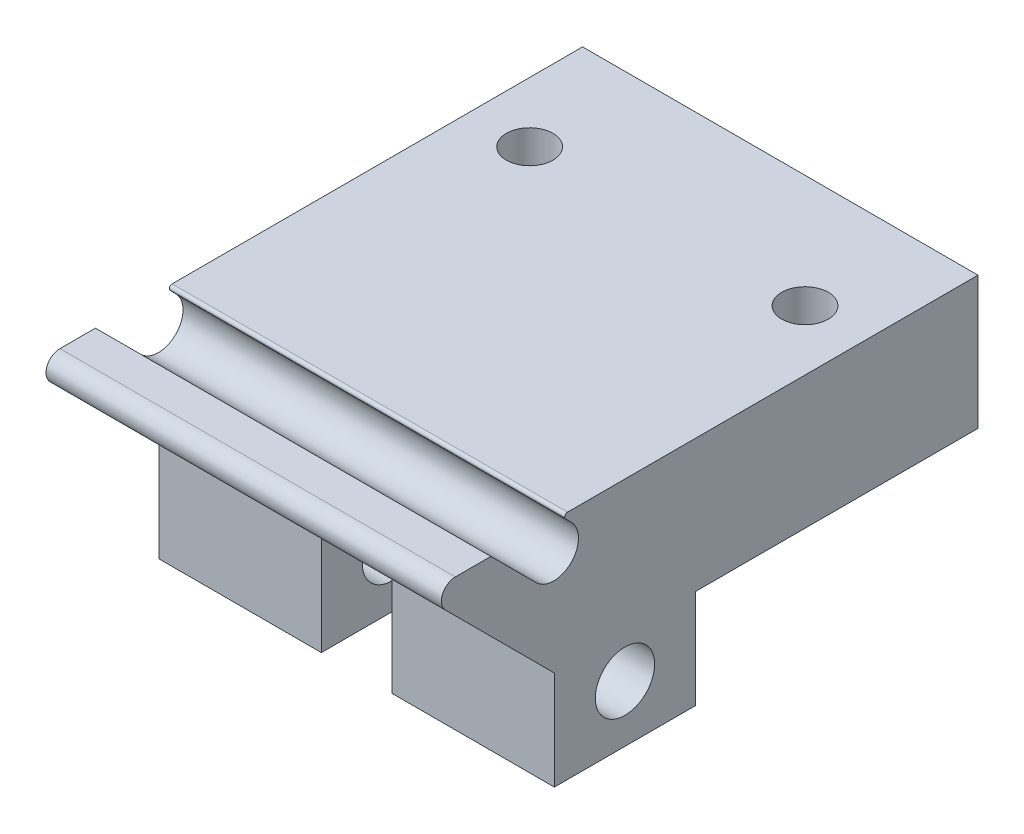
SolidWorks part; units mm, degrees
ref_plane "Front Plane" through (0, 0, 0) normal (0, 0, 1) x (1, 0, 0)
ref_plane "Top Plane" through (0, 0, 0) normal (0, 1, 0) x (1, 0, 0)
ref_plane "Right Plane" through (0, 0, 0) normal (1, 0, 0) x (0, 0, -1)
sketch "Sketch2" plane through (0, 0, 0) normal (0, 0, 1) x (1, 0, 0)
  line L1 (14, 4.699) -> (-14, 4.699)
  line L2 (14, 4.699) -> (14, -4.699)
  line L3 (14, -4.699) -> (-14, -4.699)
  line L4 (-14, 4.699) -> (-14, -4.699)
  line L5 (14, 4.699) -> (-14, -4.699) construction
  line L6 (14, -4.699) -> (-14, 4.699) construction
  point P0 (0, 0)
  dimension "D1" = 9.398
  dimension "D2" = 28
extrude "Boss-Extrude1" add sketch "Sketch2" along normal blind 30
sketch "Sketch3" plane through (14, 0, 0) normal (1, 0, 0) x (0, 0, -1)
  line L0 (-30, 0) -> (0, 0) construction
  circle A0 centre (-30, 0) radius 7.5
  dimension "D1" = 15
  dimension "D2" = 30
extrude "Cut-Extrude1" [suppressed] cut sketch "Sketch3" against normal blind 45
sketch "Sketch5" plane through (0, -4.699, 0) normal (0, -1, 0) x (1, 0, 0)
  line L0 (0, 19.5) -> (0, 0) construction
  line L5 (-2, 19.5) -> (2, 19.5)
  line L6 (-2, 19.5) -> (-2, 21)
  line L7 (-2, 21) -> (2, 21)
  line L8 (2, 19.5) -> (2, 21)
  line L15 (-2, 19.5) -> (-15, 19.5) construction
  line L16 (2, 19.5) -> (15, 19.5) construction
  line L27 (-14, 0) -> (14, 0) construction
  dimension "D1" = 4
  dimension "D2" = 1.5
  dimension "D4" = 21
extrude "Cut-Extrude3" [suppressed] cut sketch "Sketch5" against normal blind 39
fillet "Fillet1" [suppressed] radius 9
hole_wizard "M4x0.7 Tapped Hole1" positions "Sketch7" profile "Sketch6" tap size "M4x0.7" standard "ANSI Metric" end condition through all
sketch "Sketch7" plane through (0, -4.699, 0) normal (0, -1, 0) x (-1, 0, 0)
  line L0 (0, 0) -> (0, -8) construction
  line L3 (9.75, -8) -> (-9.75, -8) construction
  point P0 (-9.75, -8)
  point P2 (9.75, -8)
  dimension "D1" = 19.5
  dimension "D2" = 8
cosmetic thread "Hole Thread1" parameters "D2"=4
cosmetic thread "Hole Thread2" parameters "D2"=4
sketch "Sketch6" plane through (9.75, -4.699, 8) normal (1, 0, 0) x (0, 0, -1)
  line L0 (0, 0) -> (0, 9.398)
  line L1 (0, 9.398) -> (1.65, 9.398)
  line L2 (1.65, 9.398) -> (1.65, 0)
  line L5 (1.65, 0) -> (0, 0)
  line L11 (0, -6.35) -> (0, 107.95) construction
  dimension "Thru Tap Drill Dia." = 3.3
  dimension "Thru Tap Drill Depth" = 9.398
sketch "Sketch8" plane through (0, -4.699, 0) normal (0, -1, 0) x (1, 0, 0)
  line L0 (-14, 30) -> (14, 30) construction
  line L1 (-14, 20) -> (-2.5, 20)
  line L2 (-14, 20) -> (-14, 30)
  line L3 (-14, 30) -> (-2.5, 30)
  line L4 (-2.5, 20) -> (-2.5, 30)
  line L5 (2.5, 20) -> (14, 20)
  line L6 (2.5, 20) -> (2.5, 30)
  line L7 (2.5, 30) -> (14, 30)
  line L8 (14, 20) -> (14, 30)
  dimension "D1" = 11.5
  dimension "D2" = 10
extrude "Boss-Extrude2" add sketch "Sketch8" along normal blind 7
sketch "Sketch14" plane through (-14, 0, 0) normal (-1, 0, 0) x (0, 0, 1)
  line L0 (20, -4.699) -> (0, -4.699) construction
  line L1 (25, -7.699) -> (25, -11.699) construction
  line L2 (30, -11.699) -> (20, -11.699) construction
  circle A0 centre (25, -7.699) radius 2.1
  dimension "D1" = 4.2
  dimension "D2" = 3
extrude "Cut-Extrude6" cut sketch "Sketch14" against normal through all
sketch "Sketch16" plane through (0, 0, 30) normal (0, 0, 1) x (1, 0, 0)
  line L4 (-14, 4.699) -> (-14, -4.699)
  line L5 (14, 4.699) -> (-14, 4.699)
  line L6 (14, -4.699) -> (14, 4.699)
  line L7 (-14, -4.699) -> (14, -4.699)
  line L8 (-14, 4.699) -> (-14, -4.699)
  line L9 (14, 4.699) -> (-14, 4.699)
  line L10 (14, -4.699) -> (14, 4.699)
  line L11 (-14, -4.699) -> (14, -4.699)
  dimension "D1" = 0
extrude "Boss-Extrude3" add sketch "Sketch16" along normal blind 8
sketch "Sketch15" plane through (-14, 0, 0) normal (-1, 0, 0) x (0, 0, 1)
  line L1 (34.5, 4.699) -> (30.0452, 0.2442)
  line L2 (38, 4.699) -> (0, 4.699) construction
  line L3 (30.0452, 0.2442) -> (27.5704, 2.7191)
  line L4 (27.5704, 2.7191) -> (29.5503, 4.699)
  line L5 (29.5503, 4.699) -> (34.5, 4.699)
  line L7 (0, 4.699) -> (0, -4.699) construction
  dimension "D1" = 3.5
  dimension "D2" = 45
  dimension "D3" = 34.5
  dimension "D4" = 6.3
extrude "Cut-Extrude7" cut sketch "Sketch15" against normal through all
fillet "Fillet2" 2 edges at (0, 2.7191, 27.5704) (0, 0.2442, 30.0452) type full round first side face at (0, 3.7091, 28.5603) second side face at (0, 2.4716, 32.2726) middle face at (0, 1.4817, 28.8078)
fillet "Fillet3" radius 0.2 1 edges at (0, 4.699, 29.5503)
chamfer "Chamfer1" distance 8 angle 45 1 edges at (0, -4.699, 38)
fillet "Fillet4" 2 edges at (0, 4.699, 38) (0, 3.301, 38) type full round first side face at (0, 4.699, 36.25) second side face at (-1.5, -2.0323, 32.6667) middle face at (0, 4, 38)
